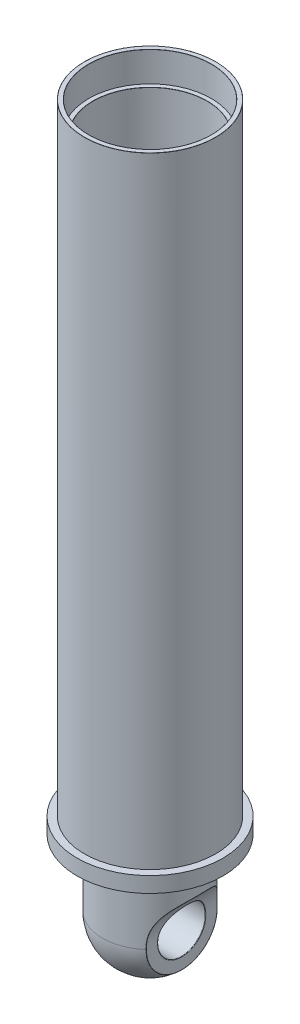
SolidWorks part; units mm, degrees
ref_plane "Front Plane" through (0, 0, 0) normal (0, 0, 1) x (1, 0, 0)
ref_plane "Top Plane" through (0, 0, 0) normal (0, 1, 0) x (1, 0, 0)
ref_plane "Right Plane" through (0, 0, 0) normal (1, 0, 0) x (0, 0, -1)
sketch "Sketch1" plane through (0, 0, 0) normal (0, 0, 1) x (1, 0, 0)
  line L0 (0, 0) -> (0, 350) construction
  line L2 (30.6, 60.4369) -> (30.6, 350)
  line L5 (30.6, 350) -> (26.6, 350)
  line L6 (26.6, 350) -> (26.6, 60.4369)
  line L7 (26.6, 60.4369) -> (0, 60.4369)
  line L8 (0, 60.4369) -> (0, 0)
  line L9 (22.1667, 53.2) -> (34.0114, 53.2)
  line L10 (34.0114, 53.2) -> (34.0114, 60.4369)
  line L11 (34.0114, 60.4369) -> (30.6, 60.4369)
  line L16 (22.1667, 22.1667) -> (22.1667, 53.2)
  line L17 (0, 0) -> (44.3568, 0) construction
  arc A2 (0, 0) -> (22.1667, 22.1667) centre (0, 22.1667) ccw
  point P4 (13.3, 60.4369)
  dimension "D9" = 22.1667
  dimension "D5" = 26.6
  dimension "D3" = 350
  dimension "D1" = 4
  dimension "D4" = 53.2
  dimension "D6" = 7.2369
  dimension "D8" = 34.0114
revolve "Revolve1" add sketch "Sketch1" angle 360 about L0 region at (32.3057, 56.9204, 0)
cosmetic thread "Cosmetic Thread1" parameters "D1"=146.4852, "D2"=53.2
sketch "Sketch2" plane through (0, 0, 0) normal (1, 0, 0) x (0, 0, -1)
  circle A0 centre (0, 22.1667) radius 11.0833
  dimension "D1" = 22.1667
  dimension "D2" = 22.1667
extrude "Cut-Extrude1" cut sketch "Sketch2" against normal through all both and the other way through all
sketch "Sketch3" plane through (0, 0, 0) normal (0, 0, 1) x (1, 0, 0)
  line L0 (0, 0) -> (0, 44.3333) construction
  line L1 (-53.3285, 44.3333) -> (-53.3285, 0)
  line L2 (35.8889, 44.3333) -> (53.3285, 44.3333)
  line L3 (14.7778, 23.2222) -> (14.7778, 0) construction
  line L4 (14.7778, 0) -> (53.3285, 0)
  line L5 (53.3285, 44.3333) -> (53.3285, 0)
  line L6 (-35.8889, 44.3333) -> (-53.3285, 44.3333)
  line L7 (-14.7778, 0) -> (-53.3285, 0)
  line L8 (-14.7778, 23.2222) -> (-14.7778, 0) construction
  arc A0 (35.8889, 44.3333) -> (14.7778, 23.2222) centre (35.8889, 23.2222) ccw construction
  arc A1 (-35.8889, 44.3333) -> (-14.7778, 23.2222) centre (-35.8889, 23.2222) cw construction
  spline S0 degree 3 poles (14.7778, 0) (14.7778, 7.3053) (14.7778, 14.6106) (14.7778, 21.916) (14.7778, 22.0611) (14.7778, 22.3514) (14.7778, 22.7868) (14.7778, 23.0771) (14.7778, 23.2222) (14.7778, 23.4294) (14.7778, 23.8438) (14.8114, 24.4654) (14.8418, 24.8787) (14.8601, 25.0851) (15.8764, 36.5572) (24.3719, 44.3333) (35.8889, 44.3333) knots 0 0 0 0 0.408919 0.408919 0.408919 0.417043 0.425168 0.433292 0.433292 0.433292 0.444889 0.456487 0.468085 0.468085 0.468085 1 1 1 1 weights 1 1 1 1 1 1 1 1 1 1 1 1 1 1 0.825097 0.825097 1
  spline S1 degree 3 poles (-14.7778, 0) (-14.7778, 7.3053) (-14.7778, 14.6106) (-14.7778, 21.916) (-14.7778, 22.0611) (-14.7778, 22.3514) (-14.7778, 22.7868) (-14.7778, 23.0771) (-14.7778, 23.2222) (-14.7778, 23.4294) (-14.7778, 23.8438) (-14.8114, 24.4654) (-14.8418, 24.8787) (-14.8601, 25.0851) (-15.8764, 36.5572) (-24.3719, 44.3333) (-35.8889, 44.3333) knots 0 0 0 0 0.408919 0.408919 0.408919 0.417043 0.425168 0.433292 0.433292 0.433292 0.444889 0.456487 0.468085 0.468085 0.468085 1 1 1 1 weights 1 1 1 1 1 1 1 1 1 1 1 1 1 1 0.825097 0.825097 1
  dimension "D4" = 21.1111
  dimension "D1" = 44.3333
  dimension "D2" = 38.5507
  dimension "D3" = 14.7778
extrude "Cut-Extrude2" cut sketch "Sketch3" against normal through all both and the other way through all
fillet "Fillet1" radius 0.2111 6 edges at (-14.8305, 24.716, 10.7861) (14.7778, 20.9729, 11.0189) (-22.0713, 39.1832, 2.0537) (-14.7778, 5.7557, 1.9131) (22.0713, 39.1832, -2.0537) (14.7778, 5.7557, -1.9131)
sketch "Sketch8" plane through (0, 350, 0) normal (0, 1, 0) x (1, 0, 0)
  circle A0 centre (0, 0) radius 28.6
  dimension "D1" = 57.2
extrude "Cut-Extrude3" cut sketch "Sketch8" against normal blind 13.9333
fillet "Fillet4" radius 0.0633 3 edges at (30.6, 350, 0) (-28.6, 350, 0) (-26.6, 336.0667, 0)
ref_plane "Plane1" through (0, 160, 0) normal (0, 1, 0) x (1, 0, 0)
equation "\"D5@Sketch1\"=\"Upper_Mount_largest_radius\""
equation "\"D1@Sketch3\"=(\"Upper_Mount_largest_radius\"/0.4)/1.5"
equation "\"D4@Sketch3\"=\"Upper_Mount_largest_radius\"/1.26"
equation "\"D1@Sketch8\"=(2*\"Upper_Mount_largest_radius\")+(\"Upper_mount_wall_thickness\")"
equation "\"Upper_Mount_largest_radius\" =26.6"
equation "\"Upper_mount_wall_thickness\" =4"
equation "\"D1@Sketch1\"=\"Upper_mount_wall_thickness\""
equation "\"D1@Cut-Extrude3\"=(\"Upper_Mount_largest_radius\"*17.6984127)/33.78787879"
equation "\"D1@Fillet4\"=\"Upper_Mount_largest_radius\"/420"
equation "\"D1@Fillet1\"=\"Upper_Mount_largest_radius\"/126"
equation "\"Lower_Mount_piston_rod_length\" =149"
equation "\"Lower_Mount_piston_rod_radius\" =3.4925"
equation "\"Piston_orifice_dia\"=0.30711"
equation "\"Spring_inner_dia\" =80"
equation "\"Spring_wire_dia\" =8"
equation "\"D1@Sketch2\"=(\"Upper_Mount_largest_radius\"/0.8)/1.5"
equation "\"D2@Sketch2\"=(\"Upper_Mount_largest_radius\"/0.8)/1.5"
equation "\"D3@Sketch3\"=(\"Upper_Mount_largest_radius\"/1.2)/1.5"
equation "\"D2@Sketch3\"=(\"Upper_Mount_largest_radius\"/0.46)/1.5"
equation "\"D2@Cosmetic Thread1\"=\"Upper_Mount_largest_radius\"*2"
equation "\"D6@Sketch1\"=\"Upper_Mount_largest_radius\"/(0.21247892*17.29871645)"
equation "\"D4@Sketch1\"=(\"Upper_Mount_largest_radius\"/0.4)/1.25"
equation "\"D8@Sketch1\"=(\"Upper_Mount_largest_radius\"/(0.21247892*2.4538608))/1.5"
equation "\"D9@Sketch1\"=(\"Upper_Mount_largest_radius\"/0.8)/1.5"
